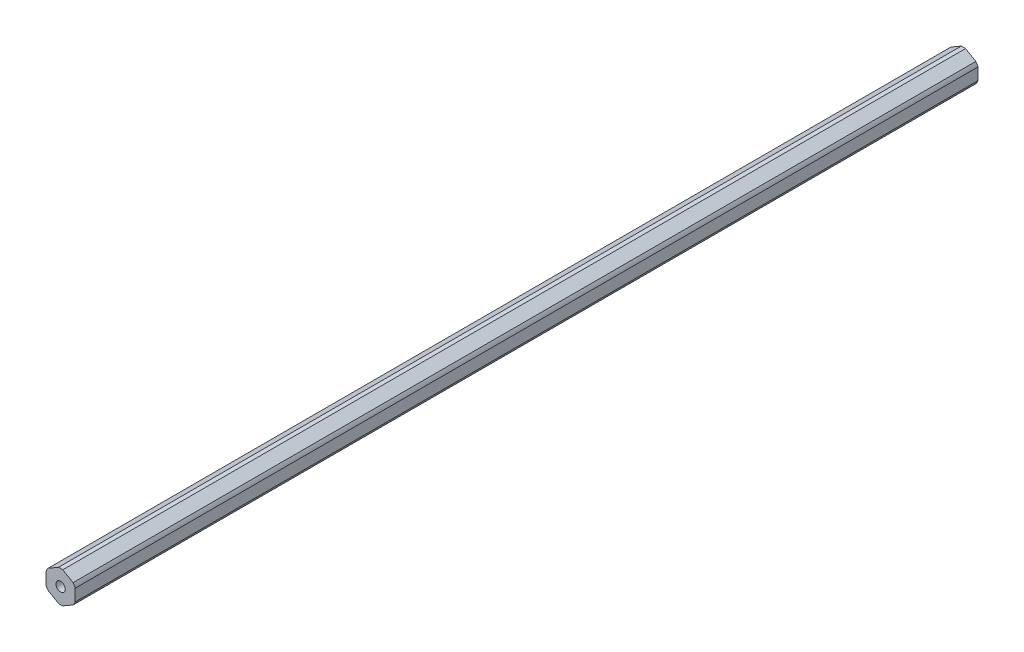
SolidWorks part; units mm, degrees
material "6061-T6 (SS)"
ref_plane "Front Plane" through (0, 0, 0) normal (0, 0, 1) x (1, 0, 0)
ref_plane "Top Plane" through (0, 0, 0) normal (0, 1, 0) x (1, 0, 0)
ref_plane "Right Plane" through (0, 0, 0) normal (1, 0, 0) x (0, 0, -1)
sketch "Sketch1" plane through (0, 0, 0) normal (0, 0, 1) x (1, 0, 0)
  line L1 (0, 7.3323) -> (-6.35, 3.6662)
  line L2 (-6.35, 3.6662) -> (-6.35, -3.6662)
  line L3 (-6.35, -3.6662) -> (0, -7.3323)
  line L4 (0, -7.3323) -> (6.35, -3.6662)
  line L5 (6.35, -3.6662) -> (6.35, 3.6662)
  line L6 (6.35, 3.6662) -> (0, 7.3323)
  circle A0 centre (0, 0) radius 6.35 construction
  circle A1 centre (0, 0) radius 6.858
  dimension "D1" = 12.7
  dimension "D2" = 13.716
extrude "Boss-Extrude1" add sketch "Sketch1" along normal mid plane 392.303 contours L5 A1 L6 L1 L2 L3 L4 region at (0, 0, 0)
sketch "Sketch2" plane through (0, 0, 196.1515) normal (0, 0, 1) x (1, 0, 0)
  circle A0 centre (0, 0) radius 2.0193
  dimension "D1" = 4.0386
extrude "Cut-Extrude1" cut sketch "Sketch2" against normal through all
